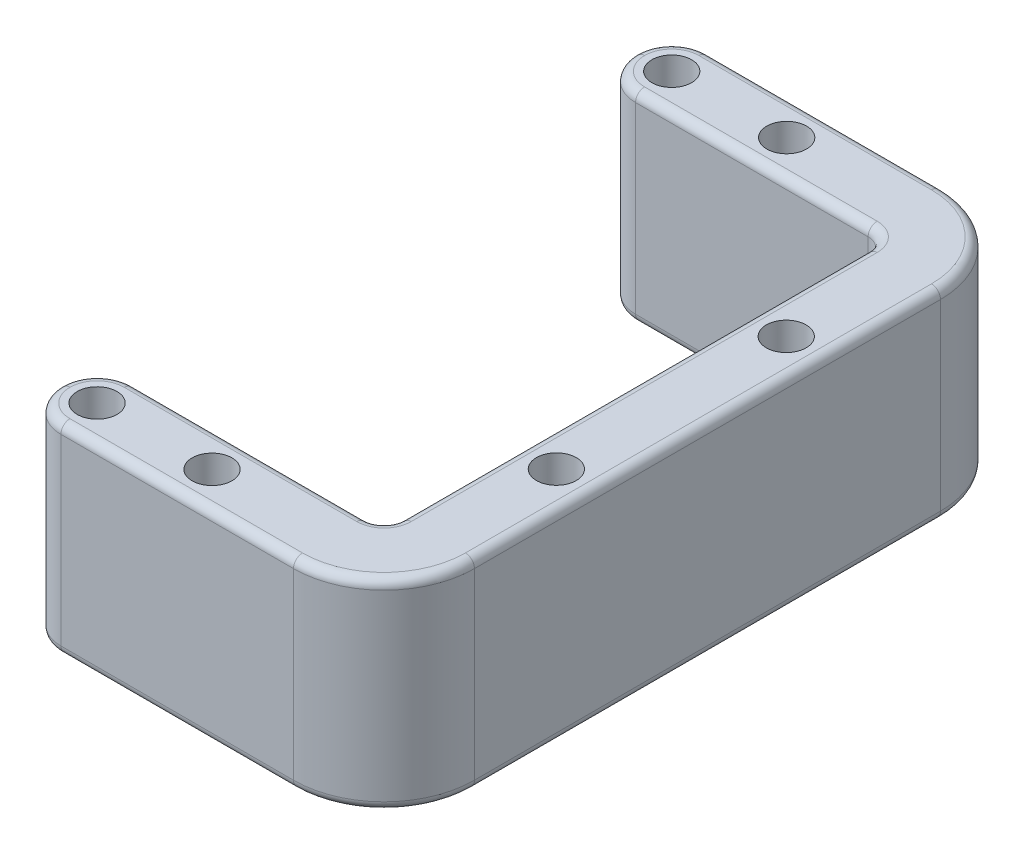
SolidWorks part; units mm, degrees
ref_plane "Front Plane" through (0, 0, 0) normal (0, 0, 1) x (1, 0, 0)
ref_plane "Top Plane" through (0, 0, 0) normal (0, 1, 0) x (1, 0, 0)
ref_plane "Right Plane" through (0, 0, 0) normal (1, 0, 0) x (0, 0, -1)
sketch "Sketch1" plane through (0, 0, 0) normal (0, 1, 0) x (1, 0, 0)
  line L1 (-4, 4) -> (27.7, 4)
  line L2 (-4, 4) -> (-4, -4)
  line L3 (-4, -4) -> (35.7, -4)
  line L5 (35.7, -4) -> (19.8585, -4)
  line L8 (27.7, 4) -> (27.7, 59.5)
  line L9 (35.7, 67.5) -> (-4, 67.5)
  line L10 (35.7, 67.5) -> (35.7, -4)
  line L11 (27.7, 59.5) -> (-4, 59.5)
  line L12 (-4, 67.5) -> (-4, 59.5)
  circle A0 centre (0, 0) radius 2.2
  circle A1 centre (12.7, 0) radius 2.2
  circle A2 centre (12.7, 63.5) radius 2.2
  circle A3 centre (0, 63.5) radius 2.2
  circle A4 centre (31.7, 44.45) radius 2.2
  circle A5 centre (31.7, 19.05) radius 2.2
  point P9 (-4, 63.5)
  point P19 (27.7, 59.5)
  point P20 (27.7, 4)
  point P24 (27.7, 31.75)
  point P27 (-4, 0)
  dimension "D1" = 4.4
  dimension "D11" = 4
  dimension "D2" = 12.7
  dimension "D3" = 63.5
  dimension "D4" = 8
  dimension "D5" = 8
  dimension "D6" = 8
  dimension "D7" = 4
  dimension "D8" = 15
  dimension "D9" = 25.4
  dimension "D10" = 12.7
extrude "Boss-Extrude1" add sketch "Sketch1" along normal blind 22.2504 contours L9 L12 L11 L8 L1 L2 L3 L10 A3 A2 A1 A0 region at (11.85, 0, -3.1822)
fillet "Fillet1" radius 10 2 edges at (35.7, 11.1252, -67.5) (35.7, 11.1252, 4)
fillet "Fillet2" radius 2 2 edges at (27.7, 11.1252, -59.5) (27.7, 11.1252, -4)
fillet "Fillet3" radius 4 4 edges at (-4, 11.1252, -67.5) (-4, 11.1252, -59.5) (-4, 11.1252, -4) (-4, 11.1252, 4)
fillet "Fillet4" radius 1 28 edges at (-2.8284, 0, 2.8284) (-2.8284, 0, -2.8284) (12.85, 0, -4) (27.1142, 0, -4.5858) (27.7, 0, -31.75) (27.1142, 0, -58.9142) (12.85, 0, -59.5) (-2.8284, 0, -60.6716) (-2.8284, 0, -66.3284) (12.85, 0, -67.5) (32.7711, 0, -64.5711) (35.7, 0, -31.75) (32.7711, 0, 1.0711) (-2.8284, 22.2504, 2.8284) (-2.8284, 22.2504, -2.8284) (12.85, 22.2504, -4) (27.1142, 22.2504, -4.5858) (27.7, 22.2504, -31.75) (27.1142, 22.2504, -58.9142) (12.85, 22.2504, -59.5) (-2.8284, 22.2504, -60.6716) (-2.8284, 22.2504, -66.3284) (12.85, 22.2504, -67.5) (32.7711, 22.2504, -64.5711) (35.7, 22.2504, -31.75) (32.7711, 22.2504, 1.0711) (12.85, 0, 4) (12.85, 22.2504, 4)
